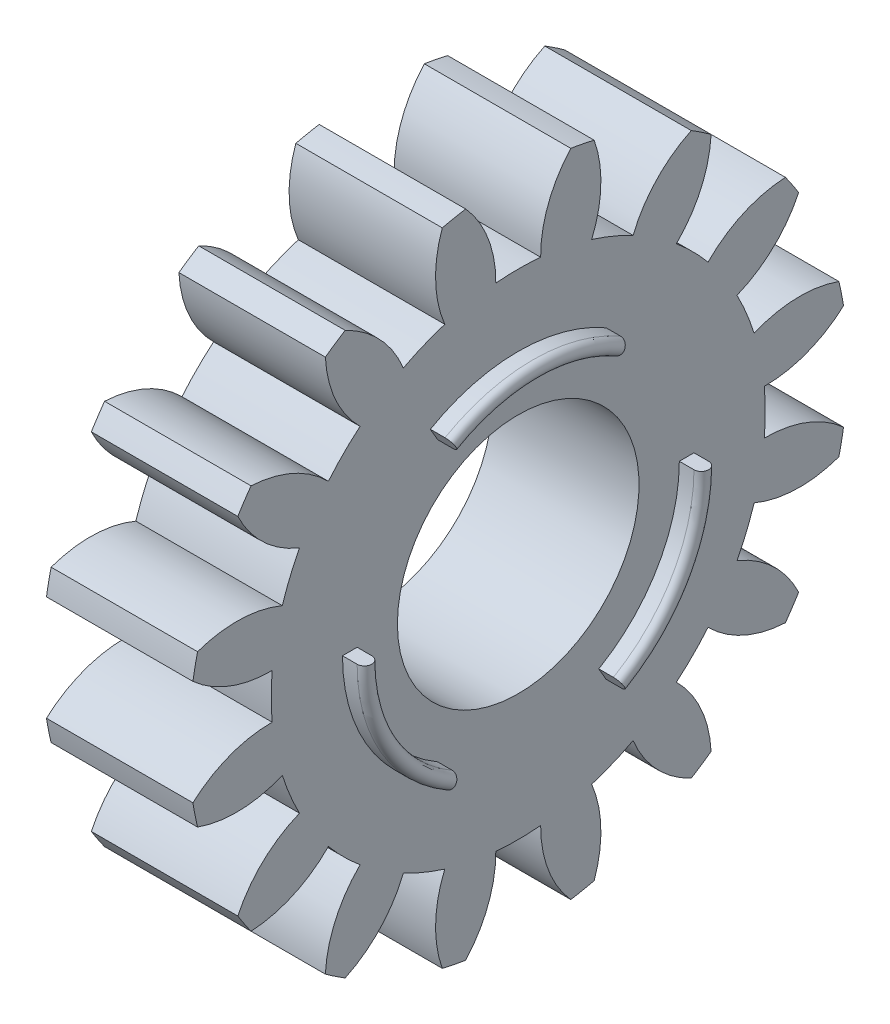
SolidWorks part; units mm, degrees
ref_plane "Plane1" through (0, 0, 0) normal (0, 0, 1) x (1, 0, 0)
ref_plane "Plane2" through (0, 0, 0) normal (0, 1, 0) x (1, 0, 0)
ref_plane "Plane3" through (0, 0, 0) normal (1, 0, 0) x (0, 0, -1)
other "Configuration Table"
sketch "HoldingSke" plane through (0, 0, 0) normal (0, 1, 0) x (1, 0, 0)
  line L0 (0, 0) -> (1.9225, -0.5513)
  line L1 (-15, 0) -> (100, 0) construction
  line L2 (0, 0) -> (-2.1039, 2.3779)
  line L3 (0, 0) -> (-11.863, 4.5341)
  line L4 (0, 0) -> (8.3015, 2.3804)
  line L5 (0, 0) -> (-46.8476, -17.4728)
  line L6 (0, 0) -> (-1.6579, -1.1186)
  line L7 (-2.1039, 2.3779) -> (8.6586, 51.2059)
  line L8 (-76.2, 54.61) -> (-75.9, 54.61)
  line L9 (-67.7845, 28.3722) -> (-49.3413, 33.142)
  line L10 (-76.2, 71.12) -> (104.1128, 71.12)
  line L11 (0, 0) -> (-2, 0)
  line L12 (-76.2, 101.6) -> (-76.181, 101.6)
  line L13 (24.9733, 27.94) -> (52.9518, 28.4284)
  line L14 (24.9733, 27.94) -> (24.9743, 27.94)
  line L15 (24.9733, 27.94) -> (100.4006, 29.5858)
  line L16 (-63.627, -0.5) -> (-12.827, -0.5)
  circle A0 centre (0, 0) radius 1
  circle A1 centre (0, 0) radius 3.374
  circle A2 centre (0, 0) radius 37.5
  circle A3 centre (0, 0) radius 1
  dimension "Num_teeth" = 16
  dimension "Pitch_radius" = 180.3128
  dimension "Width" = 2
  dimension "Thickness" = 2
sketch "BasProSke" plane through (0, 0, 0) normal (0, 1, 0) x (1, 0, 0)
  line L0 (-10, 0) -> (60, 0) construction
  line L1 (0, 0) -> (0, 4.5)
  line L2 (0, 0) -> (2, 0)
  line L3 (2, 0) -> (2, 4.5)
  line L4 (2, 4.5) -> (0, 4.5)
  dimension "Thickness" = 2
  dimension "Diameter" = 9
revolve "Base-Revolve" add sketch "BasProSke" angle 360 about L0
sketch "TooCutSke" plane through (0, 0, 0) normal (1, 0, 0) x (0, 0, -1)
  line L1 (0, 0) -> (0, 107) construction
  line L2 (0, 0) -> (-0.4253, 3.9773) construction
  line L3 (0, 0) -> (-1.5544, 7.8146) construction
  line L4 (-0.4253, 3.9773) -> (-0.7772, 3.9073) construction
  arc A0 (0.306, 3.3601) -> (-0.306, 3.3601) centre (0, 0) ccw
  arc A1 (0.7382, 4.4648) -> (-0.7382, 4.4648) centre (0, 0) ccw
  circle A2 centre (0, 0) radius 4 construction
  circle A3 centre (0, 0) radius 3.8726 construction
  arc A4 (-0.306, 3.3601) -> (-0.7382, 4.4648) centre (-1.906, 3.3711) ccw
  arc A5 (0.7382, 4.4648) -> (0.306, 3.3601) centre (1.906, 3.3711) ccw
extrude "ToothCut" cut sketch "TooCutSke" along normal through all
fillet "Breaks" [suppressed] radius 0.01 tangent propagation no
fillet "RootFillets" [suppressed] radius 0.126
pattern_circular "TeethCuts" count 16 every 22.5 about axis through (-10, 0, 0) along (1, 0, 0) of "ToothCut", "RootFillets", "Breaks"
sketch "HubNeaOneSke" plane through (0, 0, 0) normal (-1, 0, 0) x (0, 0, 1)
  circle A0 centre (0, 0) radius 3.374
  dimension "Diameter" = 6.748
extrude "HubNearOne" [suppressed] add sketch "HubNeaOneSke" along normal blind 48.0001
sketch "HubNeaBotSke" plane through (0, 0, 0) normal (-1, 0, 0) x (0, 0, 1)
  circle A0 centre (0, 0) radius 3.374
  dimension "Diameter" = 6.748
extrude "HubNearBoth" [suppressed] add sketch "HubNeaBotSke" along normal blind 24
ref_plane "FarPln" through (2, 0, 0) normal (1, 0, 0) x (0, 0, -1)
sketch "HubFarSke" plane through (2, 0, 0) normal (1, 0, 0) x (0, 0, -1)
  circle A0 centre (0, 0) radius 3.374
  dimension "Diameter" = 6.748
extrude "HubFar" [suppressed] add sketch "HubFarSke" along normal blind 24
sketch "BorSke" plane through (0, 0, 0) normal (1, 0, 0) x (0, 0, -1)
  circle A0 centre (0, 0) radius 1.65
  dimension "Diameter" = 3.3
extrude "Bore" cut sketch "BorSke" along normal mid plane 100.0001
sketch "KeySke" plane through (0, 0, 0) normal (1, 0, 0) x (0, 0, -1)
  line L0 (-0.4, 0) -> (-0.4, 1.3)
  line L1 (-0.4, 1.3) -> (0.4, 1.3)
  line L2 (0.4, 1.3) -> (0.4, 0)
  line L3 (0, 0) -> (0, 34) construction
  line L4 (-0.4, 0) -> (0.4, 0)
  dimension "Width" = 0.8
extrude "Keyway" [suppressed] cut sketch "KeySke" along normal mid plane 100.0001
pattern_circular "Keyway2" [suppressed] count 2 every 90 about axis through (-10, 0, 0) along (1, 0, 0) reverse direction yes
sketch "草图1" plane through (2, 0, 0) normal (1, 0, 0) x (0, 0, -1)
  line L0 (-1.1, 1.9053) -> (1.1, 1.9053) construction
  line L1 (-1.1, 1.9053) -> (0, 0) construction
  line L2 (0, 0) -> (1.1, 1.9053) construction
  arc A1 (-1.1, 1.9053) -> (1.1, 1.9053) centre (0, 0) cw
  arc A2 (2.2, 0) -> (1.1, -1.9053) centre (0, 0) cw
  arc A3 (-1.1, -1.9053) -> (-2.2, 0) centre (0, 0) cw
  point P11 (0, 0)
  dimension "D1" = 2.2
  dimension "D2" = 60
  dimension "D3" = 3
extrude "拉伸-薄壁2" add sketch "草图1" along normal blind 0.3 thin contours A3 | A1 | A2 thin type one direction reverse wall 0.2
fillet "圆角4" 2 edges at (2.3, -1.2, 2.0785) (2.3, -1.1, 1.9053) type full round first side face at (2.15, -1.1196, 1.9392) second side face at (2.15, -1.0263, 1.7776) middle face at (2.3, -1.073, 1.8584)
fillet "圆角5" 2 edges at (2.3, 2.2, 0) (2.3, 2.4, 0) type full round first side face at (2.15, 2.0526, 0) second side face at (2.15, 2.2392, 0) middle face at (2.3, 2.1459, 0)
fillet "圆角6" 2 edges at (2.3, -1.1, -1.9053) (2.3, -1.2, -2.0785) type full round first side face at (2.15, -1.0263, -1.7776) second side face at (2.15, -1.1196, -1.9392) middle face at (2.3, -1.073, -1.8584)
extrude "拉伸-薄壁5" add sketch "草图1<5>" against normal blind 0.3 from surface thin starting at face at (0, 0, -1.65) thin type one direction reverse wall 0.2
sketch "草图1<5>" plane through (2, 0, 0) normal (1, 0, 0) x (0, 0, -1) same geometry as "草图1"
fillet "圆角7" 2 edges at (-0.3, 2.4, 0) (-0.3, 2.2, 0) type full round first side face at (-0.15, 2.2392, 0) second side face at (-0.15, 2.0526, 0) middle face at (-0.3, 2.1459, 0)
fillet "圆角8" 2 edges at (-0.3, -1.2, 2.0785) (-0.3, -1.1, 1.9053) type full round first side face at (-0.15, -1.1196, 1.9392) second side face at (-0.15, -1.0263, 1.7776) middle face at (-0.3, -1.073, 1.8584)
fillet "圆角9" 2 edges at (-0.3, -1.1, -1.9053) (-0.3, -1.2, -2.0785) type full round first side face at (-0.15, -1.0263, -1.7776) second side face at (-0.15, -1.1196, -1.9392) middle face at (-0.3, -1.073, -1.8584)
equation "' \"Module@HoldingSke\" = 6.35"
equation "' \"Num_teeth@HoldingSke\" = 12"
equation "' \"Ap@HoldingSke\" =  20"
equation "' \"Ap@HoldingSke\" = 20"
equation "' \"Width@HoldingSke\" = 0.5 * 25.4"
equation "' \"Hub_dia@HoldingSke\"= 1 * 25.4"
equation "' \"Hub_dia@HoldingSke\" = 1 * 25.4"
equation "' \"Overall_len@HoldingSke\" = 1.0 * 25.4"
equation "' \"Bore@HoldingSke\" = 0.75 * 25.4"
equation "' \"T_dim@HoldingSke\" = 0.1 * 25.4"
equation "' \"Width@KeySke\" = 0.25 * 25.4"
equation "' \"Show_teeth@HoldingSke\" = 13"
equation "' \"Backlash@HoldingSke\" = 0.009 * 25.4"
equation "' \"Addendum_fac@HoldingSke\" = 1.0"
equation "' \"Dedendum_fac@HoldingSke\" = 1.25"
equation "' \"Dedendum_add@HoldingSke\" = 0.00005 * 25.4"
equation "' \"Clearance_fac@HoldingSke\" = 0.25"
equation "\"Pitch@HoldingSke\" = 1 / \"Module@HoldingSke\""
equation "\"Overcut_dia@TooCutSke\" = (\"Num_teeth@HoldingSke\" + 2 * \"Addendum_fac@HoldingSke\") / \"Pitch@HoldingSke\" + 0.002 * 25.4"
equation "\"Pitch_dia@TooCutSke\" = \"Num_teeth@HoldingSke\" / \"Pitch@HoldingSke\""
equation "\"Base_dia@TooCutSke\" = \"Num_teeth@HoldingSke\" / \"Pitch@HoldingSke\" * cos((\"Ap@HoldingSke\"  * 3.14159265 / 180))"
equation "\"Root_dia@TooCutSke\" = (\"Num_teeth@HoldingSke\" + 2) / \"Pitch@HoldingSke\" - 2 * (\"Addendum_fac@HoldingSke\" + \"Dedendum_fac@HoldingSke\") / \"Pitch@HoldingSke\" - \"Dedendum_add@HoldingSke\" * 2"
equation "\"Half_ang@TooCutSke\" = 180 / \"Num_teeth@HoldingSke\""
equation "\"Half_CT@TooCutSke\" = \"Num_teeth@HoldingSke\" / \"Pitch@HoldingSke\" * sin((3.14159265 / 2 / \"Num_teeth@HoldingSke\")) / 2 - 7 * \"Backlash@HoldingSke\" / 4"
equation "\"Flank_rad@TooCutSke\" = \"Num_teeth@HoldingSke\" / \"Pitch@HoldingSke\" / 5"
equation "\"Radius@RootFillets\" = \"Clearance_fac@HoldingSke\" / \"Pitch@HoldingSke\" + \"Dedendum_add@HoldingSke\""
equation "\"Break_rad@Breaks\" = 0.02 / \"Pitch@HoldingSke\""
equation "\"Thickness@HoldingSke\" = \"Width@HoldingSke\""
equation "\"OAL@HoldingSke\" = \"Thickness@HoldingSke\""
equation "\"MHD@HoldingSke\" = (\"Num_teeth@HoldingSke\" + 2) / \"Pitch@HoldingSke\" - 2 * (\"Addendum_fac@HoldingSke\" + \"Dedendum_fac@HoldingSke\")  / \"Pitch@HoldingSke\" - \"Dedendum_add@HoldingSke\" * 2"
equation "\"MBD@HoldingSke\" = (\"Num_teeth@HoldingSke\" + 2) / \"Pitch@HoldingSke\" - 2 * (\"Addendum_fac@HoldingSke\" + \"Dedendum_fac@HoldingSke\")  / \"Pitch@HoldingSke\" - \"Dedendum_add@HoldingSke\" * 2 - 0.002 * 25.4"
equation "\"MHD@HoldingSke\" = ((sgn( \"MHD@HoldingSke\" - \"Hub_dia@HoldingSke\" )-1)*( \"MHD@HoldingSke\" - \"Hub_dia@HoldingSke\" ))/-2+ \"Hub_dia@HoldingSke\""
equation "\"MBD@HoldingSke\" = ((sgn( \"MBD@HoldingSke\" - \"Bore@HoldingSke\" )-1)*( \"MBD@HoldingSke\" - \"Bore@HoldingSke\" ))/-2+ \"Bore@HoldingSke\""
equation "\"OAL@HoldingSke\" = ((sgn( \"OAL@HoldingSke\" - \"Overall_len@HoldingSke\" )+1)*( \"OAL@HoldingSke\" - \"Overall_len@HoldingSke\" ))/2 + \"Overall_len@HoldingSke\" + 0.000002 * 25.4"
equation "\"Num_teeth@TeethCuts\" = int( \"Show_teeth@HoldingSke\" ) + 1"
equation "\"Num_teeth@TeethCuts\" = ((sgn( \"Num_teeth@TeethCuts\" - \"Num_teeth@HoldingSke\" )-1)*( \"Num_teeth@TeethCuts\" - \"Num_teeth@HoldingSke\" ))/-2+ \"Num_teeth@HoldingSke\""
equation "\"Num_teeth@TeethCuts\" = ((sgn( \"Num_teeth@TeethCuts\" - 2.0)+1)*( \"Num_teeth@TeethCuts\" - 2.0))/2 +2.0"
equation "\"Angle@TeethCuts\" = 360.0 / \"Num_teeth@HoldingSke\""
equation "\"Diameter@BasProSke\" = (\"Num_teeth@HoldingSke\" + 2 * \"Addendum_fac@HoldingSke\") / \"Pitch@HoldingSke\""
equation "\"Thickness@BasProSke\"  = \"Thickness@HoldingSke\""
equation "' \"Fillet_rad@BasProSke\" =  \"Thickness@HoldingSke\" * 0.05"
equation "' \"Fillet_rad@BasProSke\" = \"Thickness@HoldingSke\" * 0.05"
equation "\"MHD@HoldingSke\" = ((sgn( \"MHD@HoldingSke\" - \"Root_dia@TooCutSke\" )-1)*( \"MHD@HoldingSke\" - \"Root_dia@TooCutSke\" ))/-2+ \"Root_dia@TooCutSke\""
equation "\"Diameter@HubNeaOneSke\" = \"MHD@HoldingSke\""
equation "\"Length@HubNearOne\" = \"OAL@HoldingSke\" - \"Thickness@BasProSke\""
equation "\"Diameter@HubNeaBotSke\" = \"MHD@HoldingSke\""
equation "\"Length@HubNearBoth\" = ( \"OAL@HoldingSke\" - \"Thickness@BasProSke\" ) / 2.0"
equation "\"Thickness@FarPln\" = \"Thickness@BasProSke\""
equation "\"Diameter@HubFarSke\" = \"MHD@HoldingSke\""
equation "\"Length@HubFar\" = ( \"OAL@HoldingSke\" - \"Thickness@BasProSke\" ) / 2.0"
equation "\"D1@Bore\" = \"OAL@HoldingSke\" * 2.0"
equation "\"D1@Keyway\" = \"OAL@HoldingSke\" * 2.0"
equation "\"Offset@KeySke\" = \"T_dim@HoldingSke\" + \"MBD@HoldingSke\" / 2.0"
